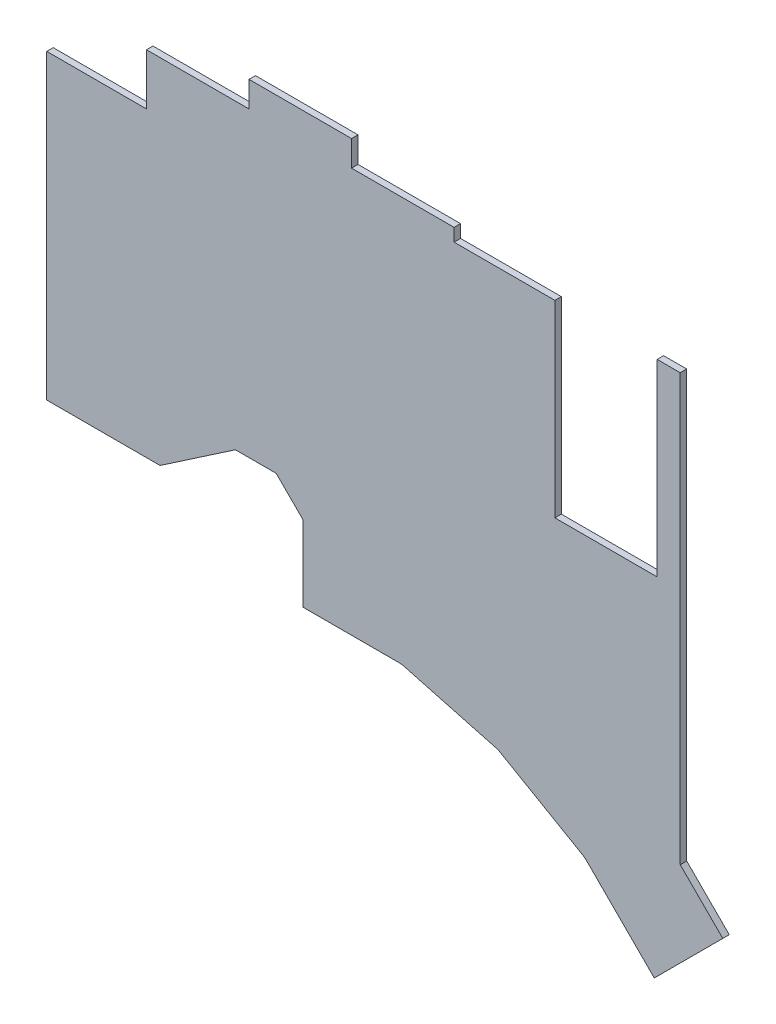
SolidWorks part; units mm, degrees
ref_plane "Plan de face" through (0, 0, 0) normal (0, 0, 1) x (1, 0, 0)
ref_plane "Plan de dessus" through (0, 0, 0) normal (0, 1, 0) x (1, 0, 0)
ref_plane "Plan de droite" through (0, 0, 0) normal (1, 0, 0) x (0, 0, -1)
sketch "Esquisse3" plane through (0, 0, 0) normal (0, 0, 1) x (1, 0, 0)
  line L0 (57.7697, 107.859) -> (75.769, 107.859) construction
  line L1 (75.769, 107.859) -> (75.769, 89.8602) construction
  line L2 (75.769, 89.8602) -> (57.7697, 89.8602) construction
  line L3 (57.7697, 89.8602) -> (57.7697, 107.859) construction
  line L4 (122.633, 13.6536) -> (132.5323, 3.7545)
  line L5 (132.5323, 3.7545) -> (142.4314, 13.6538)
  line L6 (142.4314, 13.6538) -> (132.5321, 23.5529)
  line L7 (132.5321, 23.5529) -> (122.633, 13.6536)
  line L8 (106.4982, 23.7303) -> (118.623, 16.7308)
  line L9 (118.623, 16.7308) -> (125.6222, 28.8552)
  line L10 (125.6222, 28.8552) -> (113.4975, 35.8547)
  line L11 (113.4975, 35.8547) -> (106.4982, 23.7303)
  line L12 (88.3051, 29.2895) -> (101.8291, 25.665)
  line L13 (101.8291, 25.665) -> (105.4531, 39.1873)
  line L14 (105.4531, 39.1873) -> (91.9291, 42.8117)
  line L15 (91.9291, 42.8117) -> (88.3051, 29.2895)
  line L16 (69.2947, 43.9469) -> (83.294, 43.9469)
  line L17 (83.294, 43.9469) -> (83.294, 29.9475)
  line L18 (83.294, 29.9475) -> (69.2947, 29.9475)
  line L19 (69.2947, 29.9475) -> (69.2947, 43.9469)
  line L20 (21.6697, 53.4719) -> (35.669, 53.4719)
  line L21 (35.669, 53.4719) -> (35.669, 39.4727)
  line L22 (35.669, 39.4727) -> (21.6697, 39.4727)
  line L23 (21.6697, 39.4727) -> (21.6697, 53.4719)
  line L24 (97.8697, 60.6157) -> (111.869, 60.6157)
  line L25 (111.869, 60.6157) -> (111.869, 46.6164)
  line L26 (111.869, 46.6164) -> (97.8697, 46.6164)
  line L27 (97.8697, 46.6164) -> (97.8697, 60.6157)
  line L28 (78.8197, 62.9969) -> (92.819, 62.9969)
  line L29 (92.819, 62.9969) -> (92.819, 48.9977)
  line L30 (92.819, 48.9977) -> (78.8197, 48.9977)
  line L31 (78.8197, 48.9977) -> (78.8197, 62.9969)
  line L32 (40.7197, 62.9969) -> (54.719, 62.9969)
  line L33 (54.719, 62.9969) -> (54.719, 48.9977)
  line L34 (54.719, 48.9977) -> (40.7197, 48.9977)
  line L35 (40.7197, 48.9977) -> (40.7197, 62.9969)
  line L36 (59.7697, 67.7594) -> (73.769, 67.7594)
  line L37 (73.769, 67.7594) -> (73.769, 53.7602)
  line L38 (73.769, 53.7602) -> (59.7697, 53.7602)
  line L39 (59.7697, 53.7602) -> (59.7697, 67.7594)
  line L40 (21.6697, 72.5219) -> (35.669, 72.5219)
  line L41 (35.669, 72.5219) -> (35.669, 58.5227)
  line L42 (35.669, 58.5227) -> (21.6697, 58.5227)
  line L43 (21.6697, 58.5227) -> (21.6697, 72.5219)
  line L44 (97.8697, 79.6657) -> (111.869, 79.6657)
  line L45 (111.869, 79.6657) -> (111.869, 65.6664)
  line L46 (111.869, 65.6664) -> (97.8697, 65.6664)
  line L47 (97.8697, 65.6664) -> (97.8697, 79.6657)
  line L48 (78.8197, 82.0469) -> (92.819, 82.0469)
  line L49 (92.819, 82.0469) -> (92.819, 68.0477)
  line L50 (92.819, 68.0477) -> (78.8197, 68.0477)
  line L51 (78.8197, 68.0477) -> (78.8197, 82.0469)
  line L52 (40.7197, 82.0469) -> (54.719, 82.0469)
  line L53 (54.719, 82.0469) -> (54.719, 68.0477)
  line L54 (54.719, 68.0477) -> (40.7197, 68.0477)
  line L55 (40.7197, 68.0477) -> (40.7197, 82.0469)
  line L56 (59.7697, 86.8094) -> (73.769, 86.8094)
  line L57 (73.769, 86.8094) -> (73.769, 72.8102)
  line L58 (73.769, 72.8102) -> (59.7697, 72.8102)
  line L59 (59.7697, 72.8102) -> (59.7697, 86.8094)
  line L60 (21.6697, 91.5719) -> (35.669, 91.5719)
  line L61 (35.669, 91.5719) -> (35.669, 77.5727)
  line L62 (35.669, 77.5727) -> (21.6697, 77.5727)
  line L63 (21.6697, 77.5727) -> (21.6697, 91.5719)
  line L64 (97.8697, 98.7157) -> (111.869, 98.7157)
  line L65 (111.869, 98.7157) -> (111.869, 84.7164)
  line L66 (111.869, 84.7164) -> (97.8697, 84.7164)
  line L67 (97.8697, 84.7164) -> (97.8697, 98.7157)
  line L68 (78.8197, 101.097) -> (92.819, 101.097)
  line L69 (92.819, 101.097) -> (92.819, 87.0977)
  line L70 (92.819, 87.0977) -> (78.8197, 87.0977)
  line L71 (78.8197, 87.0977) -> (78.8197, 101.097)
  line L72 (40.7197, 101.097) -> (54.719, 101.097)
  line L73 (54.719, 101.097) -> (54.719, 87.0977)
  line L74 (54.719, 87.0977) -> (40.7197, 87.0977)
  line L75 (40.7197, 87.0977) -> (40.7197, 101.097)
  line L76 (59.7697, 105.859) -> (73.769, 105.859)
  line L77 (73.769, 105.859) -> (73.769, 91.8602)
  line L78 (73.769, 91.8602) -> (59.7697, 91.8602)
  line L79 (59.7697, 91.8602) -> (59.7697, 105.859)
  line L80 (38.7197, 103.097) -> (56.719, 103.097) construction
  line L81 (56.719, 103.097) -> (56.719, 85.0977) construction
  line L82 (56.719, 85.0977) -> (38.7197, 85.0977) construction
  line L83 (38.7197, 85.0977) -> (38.7197, 103.097) construction
  line L84 (145.2598, 13.6538) -> (132.5321, 26.3813) construction
  line L85 (132.5321, 26.3813) -> (119.8046, 13.6536) construction
  line L86 (119.8046, 13.6536) -> (132.5323, 0.9261) construction
  line L87 (132.5323, 0.9261) -> (145.2598, 13.6538) construction
  line L88 (85.294, 27.9475) -> (67.2947, 27.9475) construction
  line L89 (67.2947, 27.9475) -> (67.2947, 45.9469) construction
  line L90 (67.2947, 45.9469) -> (85.294, 45.9469) construction
  line L91 (85.294, 45.9469) -> (85.294, 27.9475) construction
  line L92 (85.8556, 27.8754) -> (103.2432, 23.2155) construction
  line L93 (103.2432, 23.2155) -> (107.9026, 40.6014) construction
  line L94 (107.9026, 40.6014) -> (90.515, 45.2613) construction
  line L95 (90.515, 45.2613) -> (85.8556, 27.8754) construction
  line L96 (103.7662, 22.9981) -> (119.3552, 13.9988) construction
  line L97 (119.3552, 13.9988) -> (128.3543, 29.5874) construction
  line L98 (128.3543, 29.5874) -> (112.7653, 38.5867) construction
  line L99 (112.7653, 38.5867) -> (103.7662, 22.9981) construction
  line L100 (37.669, 37.4727) -> (19.6697, 37.4727) construction
  line L101 (19.6697, 37.4727) -> (19.6697, 55.4719) construction
  line L102 (19.6697, 55.4719) -> (37.669, 55.4719) construction
  line L103 (37.669, 55.4719) -> (37.669, 37.4727) construction
  line L104 (19.6697, 93.5719) -> (37.669, 93.5719) construction
  line L105 (37.669, 93.5719) -> (37.669, 75.5727) construction
  line L106 (37.669, 75.5727) -> (19.6697, 75.5727) construction
  line L107 (19.6697, 75.5727) -> (19.6697, 93.5719) construction
  line L108 (95.8697, 100.7157) -> (113.869, 100.7157) construction
  line L109 (113.869, 100.7157) -> (113.869, 82.7164) construction
  line L110 (113.869, 82.7164) -> (95.8697, 82.7164) construction
  line L111 (95.8697, 82.7164) -> (95.8697, 100.7157) construction
  line L112 (145.2598, 13.6538) -> (145.2598, 95.7157)
  line L113 (76.8197, 103.097) -> (94.819, 103.097) construction
  line L114 (94.819, 103.097) -> (94.819, 85.0977) construction
  line L115 (94.819, 85.0977) -> (76.8197, 85.0977) construction
  line L116 (76.8197, 85.0977) -> (76.8197, 103.097) construction
  line L117 (95.8697, 100.7157) -> (94.819, 100.7157) construction
  line L118 (76.8197, 103.097) -> (75.769, 103.097) construction
  line L119 (56.719, 103.097) -> (57.7697, 103.097) construction
  line L120 (37.669, 93.5719) -> (38.7197, 93.5719) construction
  line L121 (140.2598, 100.7157) -> (95.3443, 100.7157)
  line L122 (95.3443, 100.7157) -> (95.3443, 103.097)
  line L123 (95.3443, 103.097) -> (76.2943, 103.097)
  line L124 (76.2943, 103.097) -> (76.2943, 107.859)
  line L125 (57.2443, 103.097) -> (57.2443, 107.859)
  line L126 (57.2443, 107.859) -> (76.2943, 107.859)
  line L127 (38.1944, 93.5719) -> (38.1944, 103.097)
  line L128 (38.1944, 103.097) -> (57.2443, 103.097)
  line L129 (145.2598, 95.7157) -> (140.2598, 100.7157)
  line L130 (145.2598, 13.6538) -> (132.5323, 0.9261)
  line L131 (132.5323, 0.9261) -> (119.8046, 13.6536)
  line L132 (119.8046, 13.6536) -> (119.3552, 13.9988)
  line L133 (119.3552, 13.9988) -> (103.7662, 22.9981)
  line L134 (103.7662, 22.9981) -> (103.2432, 23.2155)
  line L135 (103.2432, 23.2155) -> (85.8556, 27.8754)
  line L136 (85.8556, 27.8754) -> (85.294, 27.9475)
  line L137 (85.294, 27.9475) -> (67.2947, 27.9475)
  line L139 (38.1944, 93.5719) -> (14.6697, 93.5719)
  line L140 (9.6697, 88.5719) -> (9.6697, 42.4727)
  line L142 (14.6697, 93.5719) -> (9.6697, 88.5719)
  line L144 (14.6697, 37.4727) -> (56.719, 37.4727)
  line L145 (56.719, 37.4727) -> (67.2947, 27.9475)
  line L146 (9.6697, 42.4727) -> (14.6697, 37.4727)
  line L147 (14.6697, 93.5719) -> (14.6697, 37.4727) construction
  line L148 (21.6697, 77.5727) -> (14.6697, 77.5727) construction
  line L149 (21.6697, 53.4719) -> (14.6697, 53.4719) construction
  line L150 (14.6697, 77.5727) -> (14.6697, 53.4719) construction
  line L153 (140.2598, 100.7157) -> (140.2598, 18.6537) construction
  line L154 (16.1697, 77.5727) -> (16.1697, 53.4719)
  line L155 (13.1697, 77.5727) -> (13.1697, 53.4719)
  line L156 (14.6697, 77.5727) -> (140.2598, 77.5727) construction
  line L159 (9.6697, 88.5719) -> (14.6697, 88.5719) construction
  line L160 (9.6697, 42.4727) -> (14.6697, 42.4727) construction
  line L161 (14.6697, 88.5719) -> (140.2598, 88.5719) construction
  line L162 (14.6697, 42.4727) -> (140.2598, 42.4727) construction
  line L163 (56.719, 37.4727) -> (56.719, 42.4727) construction
  line L164 (14.6697, 53.4719) -> (140.2598, 53.4719) construction
  line L165 (140.2598, 77.5727) -> (140.2598, 53.4719) construction
  line L166 (141.7598, 77.5727) -> (141.7598, 53.4719)
  line L167 (138.7598, 77.5727) -> (138.7598, 53.4719)
  line L169 (142.9317, 86.803) -> (143.1276, 90.0013)
  line L170 (143.1276, 90.0013) -> (140.4558, 91.7702)
  line L171 (140.4558, 91.7702) -> (137.588, 90.3408)
  line L172 (137.588, 90.3408) -> (137.392, 87.1425)
  line L173 (137.392, 87.1425) -> (140.0639, 85.3736)
  line L174 (140.0639, 85.3736) -> (142.9317, 86.803)
  circle A4 centre (14.6697, 42.4727) radius 1.6
  circle A5 centre (14.6697, 88.5719) radius 1.6
  circle A6 centre (140.2598, 88.5719) radius 1.6
  circle A7 centre (140.2598, 42.4727) radius 1.6
  circle A8 centre (56.719, 42.4727) radius 1.9483
  arc A9 (16.1697, 77.5727) -> (13.1697, 77.5727) centre (14.6697, 77.5727) ccw
  arc A10 (13.1697, 53.4719) -> (16.1697, 53.4719) centre (14.6697, 53.4719) ccw
  arc A11 (141.7598, 77.5727) -> (138.7598, 77.5727) centre (140.2598, 77.5727) ccw
  arc A12 (138.7598, 53.4719) -> (141.7598, 53.4719) centre (140.2598, 53.4719) ccw
  circle A13 centre (140.2598, 88.5719) radius 2.775 construction
  point P113 (145.2598, 100.7157)
  point P133 (9.6697, 93.5719)
  point P135 (9.6697, 27.9475)
  point P137 (9.6697, 37.4727)
  point P139 (14.6697, 65.5223)
  point P151 (140.2598, 65.5223)
  dimension "D12" = 3.2
  dimension "D13" = 3.2
  dimension "D16" = 3.2
  dimension "D17" = 3.2
  dimension "D19" = 3.8967
  dimension "D20" = 5.55
  dimension "D1" = 13.9993
  dimension "D4" = 2
  dimension "D2" = 2
  dimension "D3" = 2
  dimension "D5" = 2
  dimension "D6" = 2
  dimension "D7" = 2
  dimension "D8" = 2
  dimension "D9" = 2
  dimension "D10" = 2
  dimension "D11" = 2
sketch "Esquisse2" plane through (0, 0, 0) normal (0, 0, 1) x (1, 0, 0)
  line L0 (19.6697, 37.4727) -> (19.6697, 93.5719)
  line L1 (19.6697, 77.5727) -> (19.6697, 91.5719) construction
  line L2 (62.2947, 46.9977) -> (54.719, 46.9977)
  line L3 (143.8456, 15.068) -> (133.9463, 24.9671) construction
  line L4 (122.633, 13.6536) -> (132.5323, 3.7545) construction
  line L5 (132.5323, 3.7545) -> (142.4314, 13.6538) construction
  line L6 (142.4314, 13.6538) -> (132.5321, 23.5529) construction
  line L7 (132.5321, 23.5529) -> (122.633, 13.6536) construction
  line L8 (106.4982, 23.7303) -> (118.623, 16.7308) construction
  line L9 (118.623, 16.7308) -> (125.6222, 28.8552) construction
  line L10 (125.6222, 28.8552) -> (113.4975, 35.8547) construction
  line L11 (113.4975, 35.8547) -> (106.4982, 23.7303) construction
  line L12 (88.3051, 29.2895) -> (101.8291, 25.665) construction
  line L13 (101.8291, 25.665) -> (105.4531, 39.1873) construction
  line L14 (105.4531, 39.1873) -> (91.9291, 42.8117) construction
  line L15 (91.9291, 42.8117) -> (88.3051, 29.2895) construction
  line L16 (69.2947, 43.9469) -> (83.294, 43.9469) construction
  line L17 (83.294, 43.9469) -> (83.294, 29.9475) construction
  line L18 (83.294, 29.9475) -> (69.2947, 29.9475) construction
  line L19 (69.2947, 29.9475) -> (69.2947, 43.9469) construction
  line L20 (21.6697, 53.4719) -> (35.669, 53.4719) construction
  line L21 (35.669, 53.4719) -> (35.669, 39.4727) construction
  line L22 (35.669, 39.4727) -> (21.6697, 39.4727) construction
  line L23 (21.6697, 39.4727) -> (21.6697, 53.4719) construction
  line L24 (97.8697, 60.6157) -> (111.869, 60.6157) construction
  line L25 (111.869, 60.6157) -> (111.869, 46.6164) construction
  line L26 (111.869, 46.6164) -> (97.8697, 46.6164) construction
  line L27 (97.8697, 46.6164) -> (97.8697, 60.6157) construction
  line L28 (78.8197, 62.9969) -> (92.819, 62.9969) construction
  line L29 (92.819, 62.9969) -> (92.819, 48.9977) construction
  line L30 (92.819, 48.9977) -> (78.8197, 48.9977) construction
  line L31 (78.8197, 48.9977) -> (78.8197, 62.9969) construction
  line L32 (40.7197, 62.9969) -> (54.719, 62.9969) construction
  line L33 (54.719, 62.9969) -> (54.719, 48.9977) construction
  line L34 (54.719, 48.9977) -> (40.7197, 48.9977) construction
  line L35 (40.7197, 48.9977) -> (40.7197, 62.9969) construction
  line L36 (59.7697, 67.7594) -> (73.769, 67.7594) construction
  line L37 (73.769, 67.7594) -> (73.769, 53.7602) construction
  line L38 (73.769, 53.7602) -> (59.7697, 53.7602) construction
  line L39 (59.7697, 53.7602) -> (59.7697, 67.7594) construction
  line L40 (21.6697, 72.5219) -> (35.669, 72.5219) construction
  line L41 (35.669, 72.5219) -> (35.669, 58.5227) construction
  line L42 (35.669, 58.5227) -> (21.6697, 58.5227) construction
  line L43 (21.6697, 58.5227) -> (21.6697, 72.5219) construction
  line L44 (97.8697, 79.6657) -> (111.869, 79.6657) construction
  line L45 (111.869, 79.6657) -> (111.869, 65.6664) construction
  line L46 (111.869, 65.6664) -> (97.8697, 65.6664) construction
  line L47 (97.8697, 65.6664) -> (97.8697, 79.6657) construction
  line L48 (78.8197, 82.0469) -> (92.819, 82.0469) construction
  line L49 (92.819, 82.0469) -> (92.819, 68.0477) construction
  line L50 (92.819, 68.0477) -> (78.8197, 68.0477) construction
  line L51 (78.8197, 68.0477) -> (78.8197, 82.0469) construction
  line L52 (40.7197, 82.0469) -> (54.719, 82.0469) construction
  line L53 (54.719, 82.0469) -> (54.719, 68.0477) construction
  line L54 (54.719, 68.0477) -> (40.7197, 68.0477) construction
  line L55 (40.7197, 68.0477) -> (40.7197, 82.0469) construction
  line L56 (59.7697, 86.8094) -> (73.769, 86.8094) construction
  line L57 (73.769, 86.8094) -> (73.769, 72.8102) construction
  line L58 (73.769, 72.8102) -> (59.7697, 72.8102) construction
  line L59 (59.7697, 72.8102) -> (59.7697, 86.8094) construction
  line L60 (21.6697, 91.5719) -> (35.669, 91.5719) construction
  line L61 (35.669, 91.5719) -> (35.669, 77.5727) construction
  line L62 (35.669, 77.5727) -> (21.6697, 77.5727) construction
  line L63 (21.6697, 77.5727) -> (21.6697, 91.5719) construction
  line L64 (97.8697, 98.7157) -> (111.869, 98.7157) construction
  line L65 (111.869, 98.7157) -> (111.869, 84.7164) construction
  line L66 (111.869, 84.7164) -> (97.8697, 84.7164) construction
  line L67 (97.8697, 84.7164) -> (97.8697, 98.7157) construction
  line L68 (78.8197, 101.097) -> (92.819, 101.097) construction
  line L69 (92.819, 101.097) -> (92.819, 87.0977) construction
  line L70 (92.819, 87.0977) -> (78.8197, 87.0977) construction
  line L71 (78.8197, 87.0977) -> (78.8197, 101.097) construction
  line L72 (40.7197, 101.097) -> (54.719, 101.097) construction
  line L73 (54.719, 101.097) -> (54.719, 87.0977) construction
  line L74 (54.719, 87.0977) -> (40.7197, 87.0977) construction
  line L75 (40.7197, 87.0977) -> (40.7197, 101.097) construction
  line L76 (59.7697, 105.859) -> (73.769, 105.859) construction
  line L77 (73.769, 105.859) -> (73.769, 91.8602) construction
  line L78 (73.769, 91.8602) -> (59.7697, 91.8602) construction
  line L79 (59.7697, 91.8602) -> (59.7697, 105.859) construction
  line L80 (143.6439, 15.2697) -> (137.3523, 21.5612)
  line L82 (67.2947, 27.9475) -> (67.2947, 41.9977)
  line L83 (67.2947, 29.9475) -> (67.2947, 43.9469) construction
  line L84 (54.719, 46.9977) -> (40.7197, 46.9977) construction
  line L85 (67.2947, 41.9977) -> (62.2947, 46.9977)
  line L86 (40.7197, 37.4727) -> (54.719, 46.9977)
  line L87 (234.75, 91.8602) -> (234.75, 105.859) construction
  line L89 (114.0654, 100.7212) -> (114.0654, 100.7157)
  line L90 (114.0654, 65.7212) -> (133.0654, 65.7212)
  line L91 (133.0654, 100.7212) -> (133.0654, 100.7157)
  line L92 (156.1674, 97.7345) -> (157.1674, 97.7345)
  line L93 (114.0654, 100.7157) -> (95.3443, 100.7157)
  line L94 (220.7507, 91.8602) -> (234.75, 91.8602) construction
  line L95 (220.7507, 105.859) -> (220.7507, 91.8602) construction
  line L96 (234.75, 105.859) -> (220.7507, 105.859) construction
  line L97 (253.8, 87.0977) -> (253.8, 101.097) construction
  line L98 (239.8007, 87.0977) -> (253.8, 87.0977) construction
  line L99 (239.8007, 101.097) -> (239.8007, 87.0977) construction
  line L100 (253.8, 101.097) -> (239.8007, 101.097) construction
  line L101 (215.7, 87.0977) -> (215.7, 101.097) construction
  line L102 (201.7007, 87.0977) -> (215.7, 87.0977) construction
  line L103 (201.7007, 101.097) -> (201.7007, 87.0977) construction
  line L104 (215.7, 101.097) -> (201.7007, 101.097) construction
  line L105 (196.65, 84.7164) -> (196.65, 98.7157) construction
  line L106 (182.6507, 84.7164) -> (196.65, 84.7164) construction
  line L107 (182.6507, 98.7157) -> (182.6507, 84.7164) construction
  line L108 (196.65, 98.7157) -> (182.6507, 98.7157) construction
  line L109 (272.85, 77.5727) -> (272.85, 91.5719) construction
  line L110 (258.8507, 77.5727) -> (272.85, 77.5727) construction
  line L111 (258.8507, 91.5719) -> (258.8507, 77.5727) construction
  line L113 (272.85, 91.5719) -> (258.8507, 91.5719) construction
  line L114 (234.75, 72.8102) -> (234.75, 86.8094) construction
  line L115 (220.7507, 72.8102) -> (234.75, 72.8102) construction
  line L116 (220.7507, 86.8094) -> (220.7507, 72.8102) construction
  line L117 (234.75, 86.8094) -> (220.7507, 86.8094) construction
  line L118 (253.8, 68.0477) -> (253.8, 82.0469) construction
  line L119 (239.8007, 68.0477) -> (253.8, 68.0477) construction
  line L120 (239.8007, 82.0469) -> (239.8007, 68.0477) construction
  line L121 (135.2598, 100.7157) -> (133.0654, 100.7157)
  line L122 (95.3443, 100.7157) -> (95.3443, 103.097)
  line L123 (95.3443, 103.097) -> (76.2943, 103.097)
  line L124 (76.2943, 103.097) -> (76.2943, 107.859)
  line L125 (57.2443, 103.097) -> (57.2443, 107.859)
  line L126 (57.2443, 107.859) -> (76.2943, 107.859)
  line L127 (38.1944, 93.5719) -> (38.1944, 103.097)
  line L128 (38.1944, 103.097) -> (57.2443, 103.097)
  line L130 (145.9669, 14.3609) -> (132.5323, 0.9261)
  line L131 (132.5323, 0.9261) -> (119.8046, 13.6536)
  line L132 (119.8046, 13.6536) -> (119.3552, 13.9988)
  line L133 (119.3552, 13.9988) -> (103.7662, 22.9981)
  line L134 (103.7662, 22.9981) -> (103.2432, 23.2155)
  line L135 (103.2432, 23.2155) -> (85.8556, 27.8754)
  line L136 (85.8556, 27.8754) -> (85.294, 27.9475)
  line L137 (85.294, 27.9475) -> (67.2947, 27.9475)
  line L139 (38.1944, 93.5719) -> (19.6697, 93.5719)
  line L144 (19.6697, 37.4727) -> (40.7197, 37.4727)
  line L147 (253.8, 82.0469) -> (239.8007, 82.0469) construction
  line L148 (215.7, 68.0477) -> (215.7, 82.0469) construction
  line L149 (201.7007, 68.0477) -> (215.7, 68.0477) construction
  line L150 (201.7007, 82.0469) -> (201.7007, 68.0477) construction
  line L151 (215.7, 82.0469) -> (201.7007, 82.0469) construction
  line L152 (196.65, 65.6664) -> (196.65, 79.6657) construction
  line L153 (182.6507, 65.6664) -> (196.65, 65.6664) construction
  line L154 (182.6507, 79.6657) -> (182.6507, 65.6664) construction
  line L155 (196.65, 79.6657) -> (182.6507, 79.6657) construction
  line L156 (272.85, 58.5227) -> (272.85, 72.5219) construction
  line L157 (258.8507, 58.5227) -> (272.85, 58.5227) construction
  line L158 (258.8507, 72.5219) -> (258.8507, 58.5227) construction
  line L159 (272.85, 72.5219) -> (258.8507, 72.5219) construction
  line L160 (234.75, 53.7602) -> (234.75, 67.7594) construction
  line L161 (220.7507, 53.7602) -> (234.75, 53.7602) construction
  line L162 (220.7507, 67.7594) -> (220.7507, 53.7602) construction
  line L163 (234.75, 67.7594) -> (220.7507, 67.7594) construction
  line L164 (253.8, 48.9977) -> (253.8, 62.9969) construction
  line L165 (239.8007, 48.9977) -> (253.8, 48.9977) construction
  line L166 (239.8007, 62.9969) -> (239.8007, 48.9977) construction
  line L167 (253.8, 62.9969) -> (239.8007, 62.9969) construction
  line L168 (215.7, 48.9977) -> (215.7, 62.9969) construction
  line L169 (201.7007, 48.9977) -> (215.7, 48.9977) construction
  line L170 (201.7007, 62.9969) -> (201.7007, 48.9977) construction
  line L171 (215.7, 62.9969) -> (201.7007, 62.9969) construction
  line L172 (196.65, 46.6164) -> (196.65, 60.6157) construction
  line L173 (182.6507, 46.6164) -> (196.65, 46.6164) construction
  line L174 (182.6507, 60.6157) -> (182.6507, 46.6164) construction
  line L175 (196.65, 60.6157) -> (182.6507, 60.6157) construction
  line L176 (272.85, 39.4727) -> (272.85, 53.4719) construction
  line L177 (258.8507, 39.4727) -> (272.85, 39.4727) construction
  line L178 (258.8507, 53.4719) -> (258.8507, 39.4727) construction
  line L179 (272.85, 53.4719) -> (258.8507, 53.4719) construction
  line L180 (225.225, 29.9475) -> (225.225, 43.9469) construction
  line L181 (211.2257, 29.9475) -> (225.225, 29.9475) construction
  line L182 (211.2257, 43.9469) -> (211.2257, 29.9475) construction
  line L183 (225.225, 43.9469) -> (211.2257, 43.9469) construction
  line L184 (202.5906, 42.8117) -> (206.2145, 29.2895) construction
  line L185 (189.0666, 39.1873) -> (202.5906, 42.8117) construction
  line L186 (192.6905, 25.665) -> (189.0666, 39.1873) construction
  line L187 (206.2145, 29.2895) -> (192.6905, 25.665) construction
  line L188 (181.0222, 35.8547) -> (188.0214, 23.7303) construction
  line L189 (168.8974, 28.8552) -> (181.0222, 35.8547) construction
  line L190 (175.8967, 16.7308) -> (168.8974, 28.8552) construction
  line L191 (188.0214, 23.7303) -> (175.8967, 16.7308) construction
  line L192 (161.9875, 23.5529) -> (171.8867, 13.6536) construction
  line L193 (152.0883, 13.6538) -> (161.9875, 23.5529) construction
  line L194 (161.9874, 3.7545) -> (152.0883, 13.6538) construction
  line L195 (171.8867, 13.6536) -> (161.9874, 3.7545) construction
  line L196 (274.85, 37.4727) -> (253.8, 37.4727)
  line L197 (256.3253, 93.5719) -> (274.85, 93.5719)
  line L198 (209.2257, 27.9475) -> (227.225, 27.9475)
  line L199 (208.6641, 27.8754) -> (209.2257, 27.9475)
  line L200 (191.2764, 23.2155) -> (208.6641, 27.8754)
  line L201 (190.7535, 22.9981) -> (191.2764, 23.2155)
  line L202 (175.1645, 13.9988) -> (190.7535, 22.9981)
  line L203 (174.7151, 13.6536) -> (175.1645, 13.9988)
  line L204 (161.9873, 0.9261) -> (174.7151, 13.6536)
  line L205 (148.5527, 14.3609) -> (161.9873, 0.9261)
  line L206 (256.3253, 103.097) -> (237.2753, 103.097)
  line L207 (256.3253, 93.5719) -> (256.3253, 103.097)
  line L208 (237.2753, 107.859) -> (218.2253, 107.859)
  line L209 (237.2753, 103.097) -> (237.2753, 107.859)
  line L210 (218.2253, 103.097) -> (218.2253, 107.859)
  line L211 (199.1753, 103.097) -> (218.2253, 103.097)
  line L212 (199.1753, 100.7157) -> (199.1753, 103.097)
  line L214 (159.2598, 100.7157) -> (199.1753, 100.7157)
  line L216 (136.2598, 100.7157) -> (158.2598, 100.7157)
  line L217 (144.351, 15.9768) -> (138.3523, 21.9754)
  line L218 (253.8, 37.4727) -> (239.8007, 46.9977)
  line L219 (227.225, 41.9977) -> (232.225, 46.9977)
  line L220 (227.225, 27.9475) -> (227.225, 41.9977)
  line L222 (150.8758, 15.2697) -> (157.1674, 21.5612)
  line L223 (232.225, 46.9977) -> (239.8007, 46.9977)
  line L224 (274.85, 37.4727) -> (274.85, 93.5719)
  line L225 (150.1687, 15.9768) -> (156.1674, 21.9754)
  line L226 (145.9669, 14.3609) -> (148.5527, 14.3609)
  line L227 (115.0654, 97.7345) -> (115.0654, 68.5983)
  line L228 (156.1674, 97.7345) -> (156.1674, 21.9754)
  line L229 (145.9669, 14.3609) -> (135.9669, 24.3607) construction
  line L230 (148.5527, 14.3609) -> (158.5527, 24.3607) construction
  line L231 (132.0654, 97.7345) -> (133.0654, 97.7345)
  line L232 (115.0654, 66.7212) -> (132.0654, 66.7212)
  line L233 (132.0654, 97.7345) -> (132.0654, 68.5983)
  line L234 (114.0654, 100.7212) -> (133.0654, 100.7212)
  line L235 (158.2598, 100.7157) -> (159.2598, 100.7157)
  line L237 (114.0654, 97.7345) -> (115.0654, 97.7345)
  line L238 (135.2598, 100.7157) -> (136.2598, 100.7157)
  line L239 (133.0654, 97.7345) -> (133.0654, 68.5983)
  line L241 (138.3523, 97.7345) -> (138.3523, 21.9754)
  line L242 (114.0654, 97.7345) -> (114.0654, 68.5983)
  line L243 (133.0654, 100.7212) -> (133.0654, 65.7212) construction
  line L244 (132.0654, 100.7212) -> (132.0654, 66.7212) construction
  line L246 (114.0654, 100.7212) -> (114.0654, 65.7212) construction
  line L247 (115.0654, 100.7212) -> (115.0654, 66.7212) construction
  line L248 (137.3523, 97.7345) -> (138.3523, 97.7345)
  line L249 (143.6439, 15.2697) -> (144.351, 15.9768)
  line L250 (150.1687, 15.9768) -> (150.8758, 15.2697)
  line L251 (157.1674, 97.7345) -> (157.1674, 21.5612)
  line L252 (145.2598, 13.6538) -> (135.2598, 23.6536) construction
  line L253 (149.2598, 13.6538) -> (159.2598, 23.6536) construction
  line L261 (132.0654, 66.7212) -> (133.0654, 66.7212)
  line L262 (132.0654, 68.5983) -> (133.0654, 68.5983)
  line L263 (115.0654, 68.5983) -> (114.0654, 68.5983)
  line L264 (115.0654, 66.7212) -> (114.0654, 66.7212)
  line L265 (114.0654, 66.7212) -> (114.0654, 65.7212)
  line L266 (133.0654, 66.7212) -> (133.0654, 65.7212)
  line L267 (137.3523, 97.7345) -> (137.3523, 21.5612)
  point P98 (67.2947, 46.9977)
  point P135 (9.6697, 27.9475)
  point P216 (136.2598, 23.6536)
  point P219 (158.2598, 23.6536)
  point P226 (284.85, 27.9475)
  point P227 (227.225, 46.9977)
  dimension "D12" = 1
  dimension "D13" = 1
  dimension "D1" = 13.9993
  dimension "D4" = 2
  dimension "D3" = 2
  dimension "D7" = 35
  dimension "D6" = 19
  dimension "D2" = 2
  dimension "D5" = 2
  dimension "D11" = 1
sketch "Esquisse4" plane through (0, 0, 0) normal (0, 0, 1) x (1, 0, 0)
  line L0 (19.6697, 37.4727) -> (19.6697, 93.5719)
  line L1 (19.6697, 77.5727) -> (19.6697, 91.5719) construction
  line L2 (62.2947, 46.9977) -> (54.719, 46.9977)
  line L3 (143.8456, 15.068) -> (133.9463, 24.9671) construction
  line L4 (122.633, 13.6536) -> (132.5323, 3.7545) construction
  line L5 (132.5323, 3.7545) -> (142.4314, 13.6538) construction
  line L6 (142.4314, 13.6538) -> (132.5321, 23.5529) construction
  line L7 (132.5321, 23.5529) -> (122.633, 13.6536) construction
  line L8 (106.4982, 23.7303) -> (118.623, 16.7308) construction
  line L9 (118.623, 16.7308) -> (125.6222, 28.8552) construction
  line L10 (125.6222, 28.8552) -> (113.4975, 35.8547) construction
  line L11 (113.4975, 35.8547) -> (106.4982, 23.7303) construction
  line L12 (88.3051, 29.2895) -> (101.8291, 25.665) construction
  line L13 (101.8291, 25.665) -> (105.4531, 39.1873) construction
  line L14 (105.4531, 39.1873) -> (91.9291, 42.8117) construction
  line L15 (91.9291, 42.8117) -> (88.3051, 29.2895) construction
  line L16 (69.2947, 43.9469) -> (83.294, 43.9469) construction
  line L17 (83.294, 43.9469) -> (83.294, 29.9475) construction
  line L18 (83.294, 29.9475) -> (69.2947, 29.9475) construction
  line L19 (69.2947, 29.9475) -> (69.2947, 43.9469) construction
  line L20 (21.6697, 53.4719) -> (35.669, 53.4719) construction
  line L21 (35.669, 53.4719) -> (35.669, 39.4727) construction
  line L22 (35.669, 39.4727) -> (21.6697, 39.4727) construction
  line L23 (21.6697, 39.4727) -> (21.6697, 53.4719) construction
  line L24 (97.8697, 60.6157) -> (111.869, 60.6157) construction
  line L25 (111.869, 60.6157) -> (111.869, 46.6164) construction
  line L26 (111.869, 46.6164) -> (97.8697, 46.6164) construction
  line L27 (97.8697, 46.6164) -> (97.8697, 60.6157) construction
  line L28 (78.8197, 62.9969) -> (92.819, 62.9969) construction
  line L29 (92.819, 62.9969) -> (92.819, 48.9977) construction
  line L30 (92.819, 48.9977) -> (78.8197, 48.9977) construction
  line L31 (78.8197, 48.9977) -> (78.8197, 62.9969) construction
  line L32 (40.7197, 62.9969) -> (54.719, 62.9969) construction
  line L33 (54.719, 62.9969) -> (54.719, 48.9977) construction
  line L34 (54.719, 48.9977) -> (40.7197, 48.9977) construction
  line L35 (40.7197, 48.9977) -> (40.7197, 62.9969) construction
  line L36 (59.7697, 67.7594) -> (73.769, 67.7594) construction
  line L37 (73.769, 67.7594) -> (73.769, 53.7602) construction
  line L38 (73.769, 53.7602) -> (59.7697, 53.7602) construction
  line L39 (59.7697, 53.7602) -> (59.7697, 67.7594) construction
  line L40 (21.6697, 72.5219) -> (35.669, 72.5219) construction
  line L41 (35.669, 72.5219) -> (35.669, 58.5227) construction
  line L42 (35.669, 58.5227) -> (21.6697, 58.5227) construction
  line L43 (21.6697, 58.5227) -> (21.6697, 72.5219) construction
  line L44 (97.8697, 79.6657) -> (111.869, 79.6657) construction
  line L45 (111.869, 79.6657) -> (111.869, 65.6664) construction
  line L46 (111.869, 65.6664) -> (97.8697, 65.6664) construction
  line L47 (97.8697, 65.6664) -> (97.8697, 79.6657) construction
  line L48 (78.8197, 82.0469) -> (92.819, 82.0469) construction
  line L49 (92.819, 82.0469) -> (92.819, 68.0477) construction
  line L50 (92.819, 68.0477) -> (78.8197, 68.0477) construction
  line L51 (78.8197, 68.0477) -> (78.8197, 82.0469) construction
  line L52 (40.7197, 82.0469) -> (54.719, 82.0469) construction
  line L53 (54.719, 82.0469) -> (54.719, 68.0477) construction
  line L54 (54.719, 68.0477) -> (40.7197, 68.0477) construction
  line L55 (40.7197, 68.0477) -> (40.7197, 82.0469) construction
  line L56 (59.7697, 86.8094) -> (73.769, 86.8094) construction
  line L57 (73.769, 86.8094) -> (73.769, 72.8102) construction
  line L58 (73.769, 72.8102) -> (59.7697, 72.8102) construction
  line L59 (59.7697, 72.8102) -> (59.7697, 86.8094) construction
  line L60 (21.6697, 91.5719) -> (35.669, 91.5719) construction
  line L61 (35.669, 91.5719) -> (35.669, 77.5727) construction
  line L62 (35.669, 77.5727) -> (21.6697, 77.5727) construction
  line L63 (21.6697, 77.5727) -> (21.6697, 91.5719) construction
  line L64 (97.8697, 98.7157) -> (111.869, 98.7157) construction
  line L65 (111.869, 98.7157) -> (111.869, 84.7164) construction
  line L66 (111.869, 84.7164) -> (97.8697, 84.7164) construction
  line L67 (97.8697, 84.7164) -> (97.8697, 98.7157) construction
  line L68 (78.8197, 101.097) -> (92.819, 101.097) construction
  line L69 (92.819, 101.097) -> (92.819, 87.0977) construction
  line L70 (92.819, 87.0977) -> (78.8197, 87.0977) construction
  line L71 (78.8197, 87.0977) -> (78.8197, 101.097) construction
  line L72 (40.7197, 101.097) -> (54.719, 101.097) construction
  line L73 (54.719, 101.097) -> (54.719, 87.0977) construction
  line L74 (54.719, 87.0977) -> (40.7197, 87.0977) construction
  line L75 (40.7197, 87.0977) -> (40.7197, 101.097) construction
  line L76 (59.7697, 105.859) -> (73.769, 105.859) construction
  line L77 (73.769, 105.859) -> (73.769, 91.8602) construction
  line L78 (73.769, 91.8602) -> (59.7697, 91.8602) construction
  line L79 (59.7697, 91.8602) -> (59.7697, 105.859) construction
  line L80 (145.2598, 13.6538) -> (137.3523, 21.5612)
  line L82 (67.2947, 27.9475) -> (67.2947, 41.9977)
  line L83 (67.2947, 29.9475) -> (67.2947, 43.9469) construction
  line L84 (54.719, 46.9977) -> (40.7197, 46.9977) construction
  line L85 (67.2947, 41.9977) -> (62.2947, 46.9977)
  line L86 (40.7197, 37.4727) -> (54.719, 46.9977)
  line L87 (114.0654, 97.7345) -> (114.0654, 100.7212)
  line L89 (114.0654, 100.7212) -> (114.0654, 100.7157)
  line L90 (114.0654, 65.7212) -> (133.0654, 65.7212)
  line L91 (133.0654, 100.7212) -> (133.0654, 100.7157)
  line L93 (114.0654, 100.7157) -> (95.3443, 100.7157)
  line L94 (133.0654, 97.7345) -> (133.0654, 100.7212)
  line L121 (135.2598, 100.7157) -> (133.0654, 100.7157)
  line L122 (95.3443, 100.7157) -> (95.3443, 103.097)
  line L123 (95.3443, 103.097) -> (76.2943, 103.097)
  line L124 (76.2943, 103.097) -> (76.2943, 107.859)
  line L125 (57.2443, 103.097) -> (57.2443, 107.859)
  line L126 (57.2443, 107.859) -> (76.2943, 107.859)
  line L127 (38.1944, 93.5719) -> (38.1944, 103.097)
  line L128 (38.1944, 103.097) -> (57.2443, 103.097)
  line L130 (145.2598, 13.6538) -> (132.5323, 0.9261)
  line L131 (132.5323, 0.9261) -> (119.8046, 13.6536)
  line L132 (119.8046, 13.6536) -> (119.3552, 13.9988)
  line L133 (119.3552, 13.9988) -> (103.7662, 22.9981)
  line L134 (103.7662, 22.9981) -> (103.2432, 23.2155)
  line L135 (103.2432, 23.2155) -> (85.8556, 27.8754)
  line L136 (85.8556, 27.8754) -> (85.294, 27.9475)
  line L137 (85.294, 27.9475) -> (67.2947, 27.9475)
  line L139 (38.1944, 93.5719) -> (19.6697, 93.5719)
  line L144 (19.6697, 37.4727) -> (40.7197, 37.4727)
  line L216 (136.2598, 100.7157) -> (137.3523, 100.7157)
  line L238 (135.2598, 100.7157) -> (136.2598, 100.7157)
  line L239 (133.0654, 97.7345) -> (133.0654, 66.7212)
  line L242 (114.0654, 97.7345) -> (114.0654, 66.7212)
  line L265 (114.0654, 66.7212) -> (114.0654, 65.7212)
  line L266 (133.0654, 66.7212) -> (133.0654, 65.7212)
  line L267 (137.3523, 100.7157) -> (137.3523, 21.5612)
  point P84 (145.2598, 13.6538)
  point P91 (135.2598, 23.6536)
  point P98 (67.2947, 46.9977)
  point P135 (9.6697, 27.9475)
  point P207 (149.2598, 13.6538)
  point P215 (159.2598, 100.7157)
  point P216 (136.2598, 23.6536)
  point P218 (145.9669, 14.3609)
  point P219 (158.2598, 23.6536)
  point P220 (158.2598, 100.7157)
  point P221 (135.9669, 24.3607)
  point P225 (159.2598, 23.6536)
  point P228 (148.5527, 14.3609)
  point P229 (158.5527, 24.3607)
  point P232 (115.0654, 100.7212)
  point P233 (115.0654, 66.7212)
  point P234 (132.0654, 66.7212)
  point P235 (132.0654, 100.7212)
  dimension "D1" = 13.9993
  dimension "D4" = 2
  dimension "D3" = 2
  dimension "D7" = 35
  dimension "D6" = 19
  dimension "D2" = 2
  dimension "D5" = 2
extrude "Boss.-Extru.1" add sketch "Esquisse4" along normal blind 1.2 contours L267 L216 L238 L121 L94 L239 L266 L90 L265 L242 L87 L93 L122 L123 L124 L126 L125 L128 L127 L139 L0 L144 L86 L2 L85 L82 L137 L136 L135 L134 L133 L132 L131 L130 L80 region at (81.3905, 61.9456, 0)
